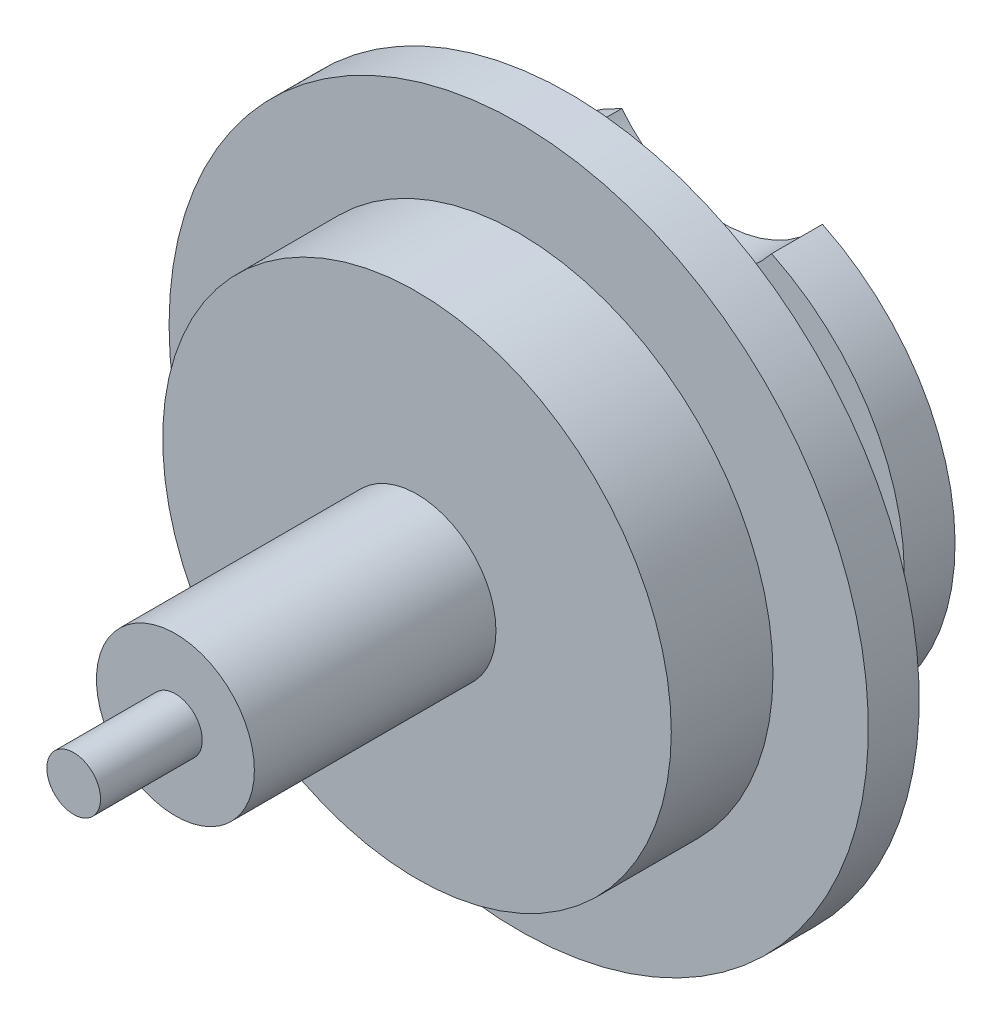
SolidWorks part; units mm, degrees
ref_plane "Alzado" through (0, 0, 0) normal (0, 0, 1) x (1, 0, 0)
ref_plane "Planta" through (0, 0, 0) normal (0, 1, 0) x (1, 0, 0)
ref_plane "Vista lateral" through (0, 0, 0) normal (1, 0, 0) x (0, 0, -1)
sketch "Sketch1" plane through (0, 0, 0) normal (0, 0, 1) x (1, 0, 0)
  circle A0 centre (0, 0) radius 0.3105
  dimension "D1" = 0.621
extrude "Boss-Extrude1" add sketch "Sketch1" against normal blind 1.35 and the other way blind 0.95
sketch "Sketch2" plane through (0, 0, 0) normal (0, 0, 1) x (1, 0, 0)
  circle A0 centre (0, 0) radius 0.1055
  dimension "D1" = 0.211
extrude "Boss-Extrude2" add sketch "Sketch2" along normal offset from surface (1.35 mm away) 0.4 up to face at (0.3105, 0, 0.95) offset beyond the face yes
extrude "Boss-Extrude3" add sketch "Sketch2<2>" against normal offset from surface (1.75 mm away) 0.4 up to face at (0.3105, 0, -1.35) offset beyond the face yes
sketch "Sketch2<2>" plane through (0, 0, 0) normal (0, 0, 1) x (1, 0, 0) same geometry as "Sketch2"
sketch "Sketch3" plane through (0, 0, 0) normal (0, 0, 1) x (1, 0, 0)
  circle A0 centre (0, 0) radius 1
  dimension "D1" = 2
extrude "Boss-Extrude4" add sketch "Sketch3" against normal blind 0.4
sketch "Sketch4" plane through (0, 0, -0.4) normal (0, 0, -1) x (-1, 0, 0)
  circle A0 centre (0, 0) radius 1.375
  dimension "D1" = 2.75
extrude "Boss-Extrude5" add sketch "Sketch4" along normal blind 0.2
sketch "Sketch5" plane through (0, 0, 0) normal (0, 0, 1) x (1, 0, 0)
  circle A0 centre (0, 0) radius 0.916
  dimension "D1" = 1.832
extrude "Boss-Extrude6" add sketch "Sketch5" against normal blind 0.2 from offset 1 offset against normal yes
sketch "Sketch6" plane through (0, 0, -1.2) normal (0, 0, -1) x (-1, 0, 0)
  line L0 (0, -1000) -> (0, 49000) construction
  circle A0 centre (0, 0) radius 1.134 construction
  circle A1 centre (0, 1.134) radius 0.5
  point P3 (0, 1.134)
  dimension "D1" = 2.268
  dimension "D2" = 1
extrude "Cut-Extrude1" cut sketch "Sketch6" against normal blind 0.2
sketch "Sketch7" plane through (0, 0, -0.6) normal (0, 0, -1) x (-1, 0, 0)
  line L0 (0, -1000) -> (0, 49000) construction
  line L1 (-1000, 0) -> (49000, 0) construction
  line L2 (-1000, 1.044) -> (49000, 1.044) construction
  ellipse E0 centre (0, 1.0437) end of major axis (0.246, 1.044) minor radius 0.078
  dimension "D1" = 1.044
extrude "Cut-Extrude2" cut sketch "Sketch7" against normal blind 0.15
